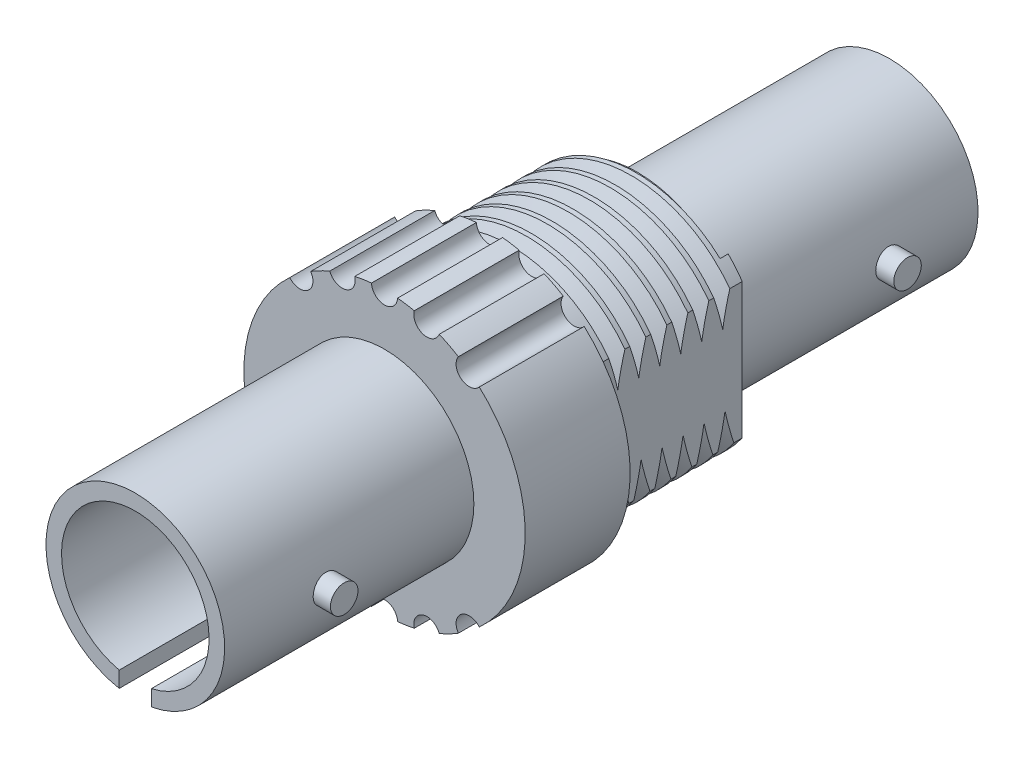
SolidWorks part; units mm, degrees
material "Chrome Stainless Steel"
ref_plane "Front Plane" through (0, 0, 0) normal (0, 0, 1) x (1, 0, 0)
ref_plane "Top Plane" through (0, 0, 0) normal (0, 1, 0) x (1, 0, 0)
ref_plane "Right Plane" through (0, 0, 0) normal (1, 0, 0) x (0, 0, -1)
sketch "Sketch1" plane through (0, 0, 0) normal (0, 0, 1) x (1, 0, 0)
  circle A0 centre (0, 0) radius 5.4483
extrude "Extrude1" add sketch "Sketch1" along normal blind 4.064
sketch "Sketch2" plane through (0, 0, 4.064) normal (0, 0, 1) x (1, 0, 0)
  circle A0 centre (0, 0) radius 3.4608
extrude "Extrude2" add sketch "Sketch2" along normal blind 9.652
sketch "Sketch4" plane through (0, 0, 0) normal (0, 0, -1) x (-1, 0, 0)
  line L2 (3.8209, -2.6246) -> (3.8209, 2.6246)
  line L4 (-3.8209, -2.6246) -> (-3.8209, 2.6246)
  line L5 (3.8209, -2.6246) -> (-3.8209, 2.6246) construction
  line L6 (3.8209, 2.6246) -> (-3.8209, -2.6246) construction
  arc A0 (-3.8209, -2.6246) -> (3.8209, -2.6246) centre (0, 0) ccw
  arc A1 (3.8209, 2.6246) -> (-3.8209, 2.6246) centre (0, 0) ccw
extrude "Extrude3" add sketch "Sketch4" along normal blind 5.969
sketch "Sketch14" plane through (0, 0, -5.969) normal (0, 0, -1) x (-1, 0, 0)
  circle A0 centre (0, 0) radius 4.064
curve "Helix/Spiral1" pitch 0.8128 height 5.527 radius 4.064 centre (0, 0, -5.969) axis (0, 0, 1) start towards (0.7071, 0.7071, 0)
sketch "Sketch15" plane through (0, 0, 0) normal (1, 0, 0) x (0, 0, -1)
  line L0 (5.8673, 4.064) -> (5.3543, 4.9947)
  line L1 (5.8673, 4.064) -> (6.3703, 4.9947)
  line L2 (6.3703, 4.9947) -> (5.3543, 4.9947)
  spline S0 degree 3 poles (5.969, 2.8737) (5.9521, 3.2502) (5.9178, 3.8596) (5.8667, 4.171) (5.8155, 3.8399) (5.7643, 2.9151) (5.7131, 1.5401) (5.6619, -0.0728) (5.6108, -1.6745) (5.5596, -3.0175) (5.5084, -3.8943) (5.4572, -4.1696) (5.4061, -3.8008) (5.3549, -2.8449) (5.3037, -1.4495) (5.2525, 0.1698) (5.2014, 1.7629) (5.1502, 3.0837) (5.099, 3.9281) (5.0478, 4.1657) (4.9967, 3.7598) (4.9455, 2.7731) (4.8943, 1.3581) (4.8431, -0.2668) (4.7919, -1.8504) (4.7408, -3.1482) (4.6896, -3.9597) (4.6384, -4.1595) (4.5872, -3.7167) (4.5361, -2.6999) (4.4849, -1.2659) (4.4337, 0.3636) (4.3825, 1.9369) (4.3314, 3.211) (4.2802, 3.9891) (4.229, 4.151) (4.1778, 3.6717) (4.1267, 2.6251) (4.0755, 1.1731) (4.0243, -0.4602) (3.9731, -2.0223) (3.9219, -3.2721) (3.8708, -4.0164) (3.8196, -4.1403) (3.7684, -3.6246) (3.7172, -2.549) (3.6661, -1.0796) (3.6149, 0.5565) (3.5637, 2.1067) (3.5125, 3.3314) (3.4614, 4.0415) (3.4102, 4.1274) (3.359, 3.5756) (3.3078, 2.4715) (3.2567, 0.9856) (3.2055, -0.6526) (3.1543, -2.1899) (3.1031, -3.3889) (3.052, -4.0645) (3.0008, -4.1122) (2.9496, -3.5246) (2.8984, -2.3926) (2.8472, -0.891) (2.7961, 0.7482) (2.7449, 2.2719) (2.6937, 3.4446) (2.6425, 4.0852) (2.5914, 4.0948) (2.5402, 3.4718) (2.489, 2.3125) (2.4378, 0.7959) (2.3867, -0.8435) (2.3355, -2.3527) (2.2843, -3.4984) (2.2331, -4.1037) (2.182, -4.0751) (2.1308, -3.417) (2.0796, -2.231) (2.0284, -0.7004) (1.9772, 0.9384) (1.9261, 2.4322) (1.8749, 3.5503) (1.8237, 4.12) (1.7725, 4.0533) (1.7214, 3.3604) (1.6702, 2.1484) (1.619, 0.6046) (1.5678, -1.0327) (1.5167, -2.5104) (1.4655, -3.6003) (1.4143, -4.1341) (1.3631, -4.0293) (1.312, -3.302) (1.2608, -2.0646) (1.2096, -0.5084) (1.1584, 1.1264) (1.1073, 2.5872) (1.0561, 3.6484) (1.0049, 4.1459) (0.9537, 4.003) (0.9025, 3.2418) (0.8514, 1.9797) (0.8002, 0.4119) (0.749, -1.2196) (0.6978, -2.6627) (0.6467, -3.6944) (0.5955, -4.1556) (0.5443, -3.9743) (0.4932, -3.1812) (0.4589, -2.3194) (0.442, -1.845) knots 0 0 0 0 0.009259 0.018519 0.027778 0.037037 0.046296 0.055556 0.064815 0.074074 0.083333 0.092593 0.101852 0.111111 0.12037 0.12963 0.138889 0.148148 0.157407 0.166667 0.175926 0.185185 0.194444 0.203704 0.212963 0.222222 0.231481 0.240741 0.25 0.259259 0.268519 0.277778 0.287037 0.296296 0.305556 0.314815 0.324074 0.333333 0.342593 0.351852 0.361111 0.37037 0.37963 0.388889 0.398148 0.407407 0.416667 0.425926 0.435185 0.444444 0.453704 0.462963 0.472222 0.481481 0.490741 0.5 0.509259 0.518519 0.527778 0.537037 0.546296 0.555556 0.564815 0.574074 0.583333 0.592593 0.601852 0.611111 0.62037 0.62963 0.638889 0.648148 0.657407 0.666667 0.675926 0.685185 0.694444 0.703704 0.712963 0.722222 0.731481 0.740741 0.75 0.759259 0.768519 0.777778 0.787037 0.796296 0.805556 0.814815 0.824074 0.833333 0.842593 0.851852 0.861111 0.87037 0.87963 0.888889 0.898148 0.907407 0.916667 0.925926 0.935185 0.944444 0.953704 0.962963 0.972222 0.981481 0.990741 1 1 1 1 construction
sweep "Cut-Sweep1" cut profiles "Sketch15" path "Helix/Spiral1"
sketch "Sketch5" plane through (0, 0, -5.969) normal (0, 0, -1) x (-1, 0, 0)
  circle A0 centre (0, 0) radius 3.429
extrude "Extrude4" add sketch "Sketch5" along normal blind 9.525
sketch "Sketch6" plane through (0, 0, 0) normal (0, 0, -1) x (-1, 0, 0)
  circle A0 centre (0, 5.4483) radius 0.5065
  circle A1 centre (0, 0) radius 5.4483 construction
  circle A2 centre (-1.6427, 5.1948) radius 0.508
  circle A3 centre (1.6427, 5.1948) radius 0.508
  circle A4 centre (0, -5.4483) radius 0.508
  circle A5 centre (-1.6427, -5.1948) radius 0.508
  circle A6 centre (1.6083, -5.2055) radius 0.508
  circle A7 centre (3.2797, 4.3506) radius 0.508
  circle A8 centre (-3.2797, 4.3506) radius 0.508
  circle A9 centre (-3.2797, -4.3506) radius 0.508
  circle A10 centre (3.2797, -4.3506) radius 0.508
extrude "Extrude5" cut sketch "Sketch6" against normal blind 4.572
sketch "Sketch7" plane through (0, 0, 0) normal (1, 0, 0) x (0, 0, -1)
  circle A0 centre (-9.7536, 0) radius 0.5334
extrude "Extrude6" add sketch "Sketch7" along normal blind 4.1275 and the other way blind 4.1275
sketch "Sketch9" plane through (0, 0, 13.716) normal (0, 0, 1) x (1, 0, 0)
  line L2 (0.6223, -2.7889) -> (0.6223, -3.6195)
  line L3 (0.6223, -3.6195) -> (-0.6223, -3.6195)
  line L4 (-0.6223, -2.7889) -> (-0.6223, -3.6195)
  arc A0 (0.6223, -2.7889) -> (-0.6223, -2.7889) centre (0, 0) ccw
  point P3 (0, -2.8575)
extrude "Extrude8" cut sketch "Sketch9" against normal blind 7.3914
sketch "Sketch10" plane through (0, 0, 0) normal (1, 0, 0) x (0, 0, -1)
  circle A0 centre (12.065, 0) radius 0.5334
extrude "Extrude9" add sketch "Sketch10" along normal blind 4.1275 and the other way blind 4.1275
sketch "Sketch11" plane through (0, 0, -15.494) normal (0, 0, -1) x (-1, 0, 0)
  line L1 (0.6223, -3.6195) -> (-0.6223, -3.6195)
  line L2 (0.6223, -3.6195) -> (0.6223, -2.7889)
  line L4 (-0.6223, -3.6195) -> (-0.6223, -2.7889)
  arc A0 (0.6223, -2.7889) -> (-0.6223, -2.7889) centre (0, 0) ccw
  point P3 (0, -2.8575)
extrude "Extrude10" cut sketch "Sketch11" against normal blind 7.493
sketch "Sketch12" plane through (0, 0, 6.3246) normal (0, 0, 1) x (1, 0, 0)
  circle A0 centre (0, 0) radius 1.2954
extrude "Extrude11" cut sketch "Sketch12" against normal through all
fillet "Fillet2" radius 1.2446 2 edges at (1.2954, 0, 6.3246) (-1.2954, 0, -8.001)
